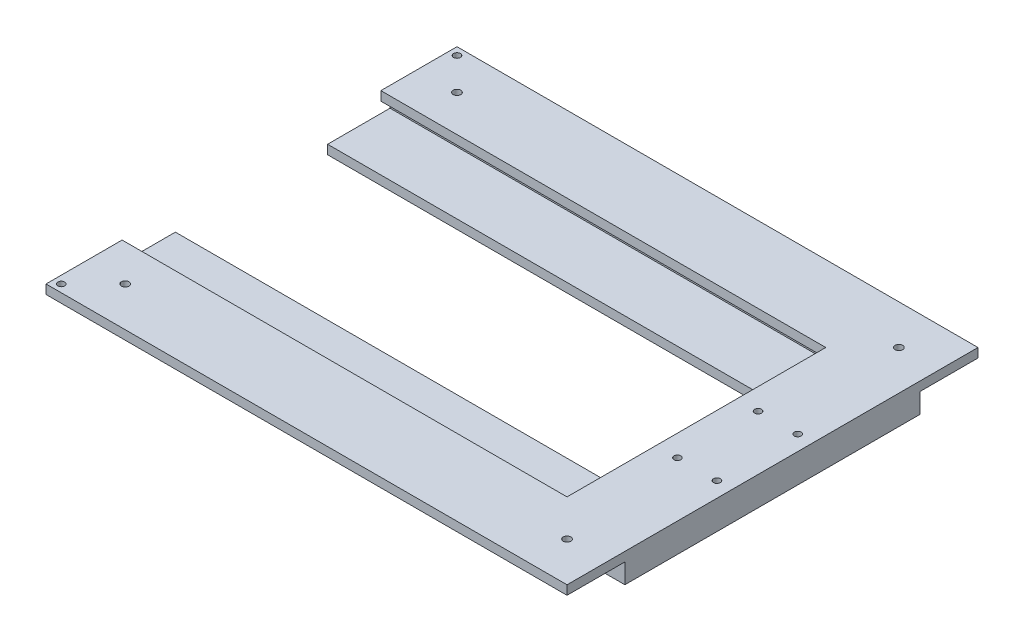
SolidWorks part; units mm, degrees
ref_plane "Спереди" through (0, 0, 0) normal (0, 0, 1) x (1, 0, 0)
ref_plane "Сверху" through (0, 0, 0) normal (0, 1, 0) x (1, 0, 0)
ref_plane "Справа" through (0, 0, 0) normal (1, 0, 0) x (0, 0, -1)
sketch "Эскиз1" plane through (0, 0, 0) normal (0, 1, 0) x (1, 0, 0)
  line L0 (50, -77.9215) -> (50, -347.9215)
  line L1 (-292.3, -77.9215) -> (50, -77.9215)
  line L2 (-292.3, -77.9215) -> (-292.3, -127.9215)
  line L3 (-292.3, -347.9215) -> (50, -347.9215)
  line L5 (-292.3, -127.9215) -> (0, -127.9215)
  line L7 (-292.3, -297.9215) -> (0, -297.9215)
  line L13 (-292.3, -297.9215) -> (-292.3, -347.9215)
  line L22 (0, -127.9215) -> (0, -297.9215)
  dimension "D1" = 342.3
  dimension "D12" = 50
  dimension "D2" = 270
  dimension "D3" = 50
  dimension "D4" = 50
  dimension "D9" = 50
  dimension "D8" = 77.9215
extrude "Бобышка-Вытянуть2" add sketch "Эскиз1" along normal blind 6
sketch "Эскиз2" plane through (0, 0, 0) normal (0, -1, 0) x (1, 0, 0)
  line L0 (-292.3, 127.9215) -> (0, 127.9215) construction
  line L5 (50, 347.9215) -> (50, 77.9215) construction
  line L6 (0, 297.9215) -> (-292.3, 297.9215) construction
  line L18 (50, 309.9215) -> (50, 115.9215)
  line L20 (6, 303.9215) -> (6, 121.9215)
  line L21 (-292.3, 77.9215) -> (-292.3, 127.9215) construction
  line L22 (50, 115.9215) -> (-292.3, 115.9215)
  line L24 (6, 121.9215) -> (-292.3, 121.9215)
  line L25 (-292.3, 115.9215) -> (-292.3, 121.9215)
  line L26 (-292.3, 297.9215) -> (-292.3, 347.9215) construction
  line L27 (50, 309.9215) -> (-292.3, 309.9215)
  line L29 (6, 303.9215) -> (-292.3, 303.9215)
  line L30 (-292.3, 309.9215) -> (-292.3, 303.9215)
  dimension "D1" = 44
  dimension "D2" = 6
  dimension "D3" = 6
  dimension "D4" = 6
  dimension "D5" = 6
extrude "Бобышка-Вытянуть3" add sketch "Эскиз2" along normal blind 7
sketch "Эскиз4" plane through (0, 6, 0) normal (0, 1, 0) x (1, 0, 0)
  line L0 (50, -77.9215) -> (-292.3, -77.9215) construction
  line L1 (-292.3, -77.9215) -> (-292.3, -127.9215) construction
  circle A0 centre (-266.3, -103.9215) radius 2.5
  dimension "D1" = 5
  dimension "D2" = 26
  dimension "D3" = 26
extrude "Вырез-Вытянуть1" cut sketch "Эскиз4" against normal through all
pattern_linear "Линейный массив2" count 2 spacing 290.3 along (1, 0, 0) count 2 spacing 218 along (0, 0, 1) of "Вырез-Вытянуть1"
sketch "Эскиз5" plane through (0, -7, 0) normal (0, -1, 0) x (1, 0, 0)
  line L8 (50, 309.9215) -> (-292.3, 309.9215)
  line L9 (-292.3, 309.9215) -> (-292.3, 262.9215)
  line L10 (-292.3, 262.9215) -> (0, 262.9215)
  line L11 (0, 262.9215) -> (0, 162.9215)
  line L12 (0, 162.9215) -> (-292.3, 162.9215)
  line L13 (-292.3, 162.9215) -> (-292.3, 115.9215)
  line L14 (-292.3, 115.9215) -> (50, 115.9215)
  line L15 (50, 115.9215) -> (50, 309.9215)
  point P0 (0, 212.9215)
  point P9 (50, 212.9215)
  dimension "D1" = 100
extrude "Бобышка-Вытянуть4" add sketch "Эскиз5" along normal blind 6
sketch "Эскиз6" plane through (0, -13, 0) normal (0, -1, 0) x (1, 0, 0)
  line L0 (40, 212.9215) -> (50, 212.9215) construction
  line L1 (40, 186.4215) -> (14, 186.4215) construction
  line L2 (40, 186.4215) -> (40, 239.4215) construction
  line L3 (40, 239.4215) -> (14, 239.4215) construction
  line L4 (14, 186.4215) -> (14, 239.4215) construction
  line L5 (50, 115.9215) -> (50, 309.9215) construction
  circle A1 centre (14, 239.4215) radius 2.25
  circle A2 centre (40, 239.4215) radius 2.25
  circle A3 centre (40, 186.4215) radius 2.25
  circle A4 centre (14, 186.4215) radius 2.25
  point P4 (50, 212.9215)
  point P6 (40, 212.9215)
  dimension "D4" = 4.5
  dimension "D1" = 53
  dimension "D2" = 26
  dimension "D3" = 10
extrude "Вырез-Вытянуть2" cut sketch "Эскиз6" against normal through all
sketch "Эскиз7" plane through (0, 0, 0) normal (0, -1, 0) x (1, 0, 0)
  line L0 (-292.3, 337.9215) -> (-282.3, 347.9215) construction
  line L1 (-292.3, 347.9215) -> (-282.3, 347.9215) construction
  line L2 (-292.3, 347.9215) -> (-292.3, 337.9215) construction
  line L3 (-292.3, 337.9215) -> (-282.3, 337.9215) construction
  line L4 (-282.3, 347.9215) -> (-282.3, 337.9215) construction
  line L5 (-292.3, 347.9215) -> (-282.3, 337.9215) construction
  line L6 (-282.3, 87.9215) -> (-292.3, 77.9215) construction
  line L7 (-292.3, 77.9215) -> (-282.3, 77.9215) construction
  line L8 (-292.3, 77.9215) -> (-292.3, 87.9215) construction
  line L9 (-292.3, 87.9215) -> (-282.3, 87.9215) construction
  line L10 (-282.3, 77.9215) -> (-282.3, 87.9215) construction
  line L11 (-292.3, 87.9215) -> (-282.3, 77.9215) construction
  circle A0 centre (-287.3, 342.9215) radius 2.25
  circle A1 centre (-287.3, 82.9215) radius 2.25
  point P12 (-287.3, 82.9215)
  dimension "D3" = 4.5
  dimension "D6" = 4.5
  dimension "D1" = 10
  dimension "D2" = 10
  dimension "D4" = 10
  dimension "D5" = 10
extrude "Вырез-Вытянуть3" cut sketch "Эскиз7" against normal through all
equation "\"Ширина груза\"= 160"
equation "\"Глубина груза\"= 240"
equation "\"Высота груза\"= 160"
equation "\"Ширина ячейки\"= \"Ширина груза\" + 10"
equation "\"Глубина ячейки\"= \"Глубина груза\" + 10"
equation "\"Высота ячейки\"= \"Высота груза\" + 10 + 13"
equation "\"Колво ячеек ширина\"= 2"
equation "\"Колво ячеек высота\"= 2"
equation "\"Толщина стенки\" = \"Толщина тонких панелей\""
equation "\"Крепление дверцы\"= 5 "
equation "\"Ширина рейки\"= \"Толщина шестерни\""
equation "\"Высота рейки\"= 20"
equation "\"Высота пола\" = 2*\"Толщина тонких панелей\""
equation "\"Колво полозьев\"= 5"
equation "\"Отступ рейки\"= 20"
equation "\"Глубина каретки\"= \"Глубина ячейки\" + 30 + \"Мотор Y высота корпуса\" + 20"
equation "\"Длинна рейки\" = (\"Ширина ячейки\"+\"Толщина вертикальных стенок\"+\"Крепление дверцы\")*\"Колво ячеек ширина\"+\"Ширина ячейки выгрузки\"*\"Колво выгрузки\"+\"Толщина вертикальных стенок\"+2*\"Отступ крепления мотора фиксации\"-\"Крепление дверцы\"*\"Колво ячеек ширина\""
equation "\"Отступ шпильки\"= 26"
equation "\"Диаметр шпильки\"= 5"
equation "\"Длинна шпильки\" = (\"Высота ячейки\"+\"Толщина горизонтальных плит\"+\"Высота пола\")*\"Колво ячеек высота\"+2*(\"Толщина горизонтальных плит\"+\"Отступ рейки\")"
equation "\"D2@Эскиз1\"=\"Ширина ячейки\" + \"Ширина пластины\" * 2 "
equation "\"D9@Эскиз1\"=\"Ширина пластины\""
equation "\"D3@Эскиз1\"=\"Ширина пластины\""
equation "\"D4@Эскиз1\"= \"Ширина пластины\""
equation "\"Ширина пластины\"= 50  "
equation "\"D1@Бобышка-Вытянуть2\"=\"Толщина стенки\""
equation "\"D1@Эскиз4\"= \"Диаметр шпильки\""
equation "\"D4@Линейный массив2\"=\"Ширина ячейки\" + \"Ширина пластины\" * 2  - \"Отступ шпильки\" * 2"
equation "\"D1@Эскиз1\"= \"Глубина каретки\""
equation "\"D3@Линейный массив2\"= \"Глубина каретки\" - \"Отступ шпильки\" * 2"
equation "\"D2@Эскиз4\"=\"Отступ шпильки\""
equation "\"D3@Эскиз4\"= \"Отступ шпильки\""
equation "\"D1@Эскиз2\"= \"Ширина пластины\" - \"Толщина стенки\""
equation "\"D2@Эскиз2\"= \"Толщина стенки\""
equation "\"D3@Эскиз2\"= \"Толщина стенки\""
equation "\"D4@Эскиз2\"= \"Толщина стенки\""
equation "\"D5@Эскиз2\"= \"Толщина стенки\""
equation "\"D1@Бобышка-Вытянуть4\"= \"Толщина стенки\""
equation "\"Вы\"=20"
equation "\"D1@Бобышка-Вытянуть3\"=\"Высота пола\" - 5"
equation "\"Высота зона выгрузки\"= \"Высота ячейки\" * 2 + \"Толщина стенки\" * 2"
equation "\"Колво выгрузки\"= 1"
equation "\"Ширина ячейки выгрузки\" = \"Ширина ячейки\"+\"Толщина вертикальных стенок\"+2*\"Отступ крепления мотора фиксации\""
equation "\"Отступ крепления мотора фиксации\" = (\"Ширина пластины\"+20-\"Толщина вертикальных стенок\")/2"
equation "\"Мотор X ширина корпуса\"= 42.3"
equation "\"Мотор X высота корпуса\"= 42.3"
equation "\"Мотор X длина корпуса\"= 40"
equation "\"Мотор X вылет вала\"= 19.8"
equation "\"Мотор Y ширина корпуса\"= 42.3"
equation "\"Мотор Y высота корпуса\"= 42.3"
equation "\"Мотор Y длина корпуса\"= 48"
equation "\"Мотор Y вылет вала\"= 30"
equation "\"Мотор Z ширина корпуса\"= 42"
equation "\"Мотор Z высота корпуса\"= 42"
equation "\"Мотор Z длина корпуса\"= 40"
equation "\"Мотор Z вылет вала\"= 23"
equation "\"Мотор диаметр вала ПРЕДВ\"= 5"
equation "\"Мотор шаг крепления ПРЕДВ\"= 31"
equation "\"Мотор диаметр отверстий ПРЕДВ\"= 3"
equation "\"Мотор глубина отверстий ПРЕДВ\"= 4.5"
equation "\"Мотор диаметр буртика ПРЕДВ\"= 22"
equation "\"Мотор высота буртика ПРЕДВ\"= 2"
equation "\"Мотор диаметр шкива ПРЕДВ\"= 16"
equation "\"Мотор длина шкива ПРЕДВ\"= 12"
equation "\"Мотор отступ шкива ПРЕДВ\"= 5"
equation "\"Мотор X шаг градусов\"= 1.8"
equation "\"Мотор X ток А\"= 1.5"
equation "\"Мотор X сопротивление Ом\"= 1.3"
equation "\"Мотор X индуктивность мГн\"= 2"
equation "\"Мотор Y шаг градусов\"= 1.8"
equation "\"Мотор Y ток А\"= 2.2"
equation "\"Мотор Y сопротивление Ом\"= 0.9"
equation "\"Мотор Y индуктивность мГн\"= 2"
equation "\"Мотор Z шаг градусов\"= 1.8"
equation "\"Мотор Z ток А\"= 1"
equation "\"Мотор Z сопротивление Ом\"= 4"
equation "\"Мотор Z индуктивность мГн\"= 8"
equation "\"Мотор Y диаметр ротора\"= 25.78"
equation "\"Толщина тонких панелей\" = 6"
equation "\"Толщина вертикальных стенок\" = 6"
equation "\"Толщина горизонтальных плит\" = 6"
equation "\"Базовая высота корпуса\"= (\"Высота ячейки\"+\"Толщина тонких панелей\"+\"Высота пола\")*\"Колво ячеек высота\"+6*\"Толщина тонких панелей\"+\"Мотор X ширина корпуса\"+\"Мотор Y ширина корпуса\"+75"
equation "\"Высота корпуса\"= (\"Высота ячейки\"+\"Толщина горизонтальных плит\"+\"Высота пола\")*\"Колво ячеек высота\"+2*\"Толщина горизонтальных плит\"+4*\"Толщина тонких панелей\"+\"Мотор X ширина корпуса\"+\"Мотор Y ширина корпуса\"+75"
equation "\"Смещение центра корпуса\"= (\"Высота корпуса\"-\"Базовая высота корпуса\")/2-(\"Толщина горизонтальных плит\"-\"Толщина тонких панелей\")"
equation "\"Отметка пола\"= -\"Базовая высота корпуса\"/2+\"Толщина тонких панелей\""
equation "\"Отметка потолка\"= \"Отметка пола\"+\"Высота корпуса\"-2*\"Толщина горизонтальных плит\""
equation "\"Отметка верхней полки\"= \"Отметка потолка\"-(28+\"Толщина тонких панелей\")-\"Высота ячейки\"-\"Высота пола\""
equation "\"Отметка нижней полки\"= \"Отметка верхней полки\"-\"Высота ячейки\"-\"Высота пола\"-\"Толщина горизонтальных плит\""
equation "\"Толщина шестерни\"= 10"
